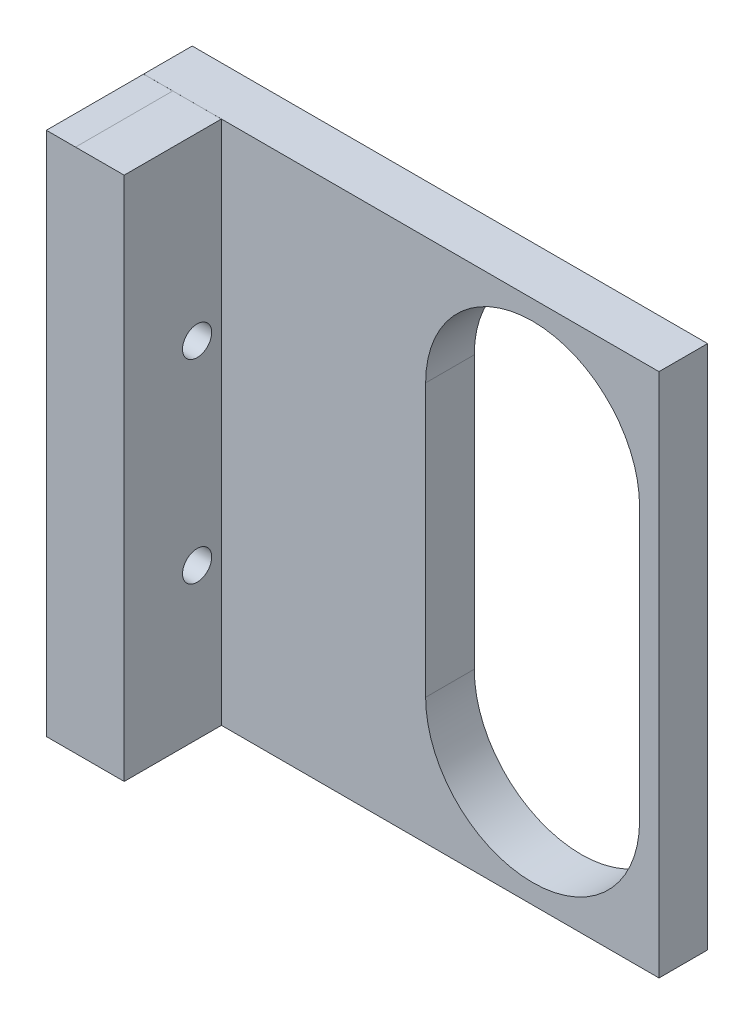
SolidWorks part; units mm, degrees
ref_plane "前视基准面" through (0, 0, 0) normal (0, 0, 1) x (1, 0, 0)
ref_plane "上视基准面" through (0, 0, 0) normal (0, 1, 0) x (1, 0, 0)
ref_plane "右视基准面" through (0, 0, 0) normal (1, 0, 0) x (0, 0, -1)
other "Configuration Table"
sketch "草图2" plane through (0, 0, 0) normal (0, 0, 1) x (1, 0, 0)
  line L0 (13, 4.25) -> (-40, 4.25)
  line L1 (-40, 4.25) -> (-40.0039, 58.25)
  line L2 (13, 4.25) -> (12.9961, 58.25)
  line L3 (-40.0039, 58.25) -> (12.9961, 58.25)
  dimension "D1" = 53
  dimension "D2" = 54
  dimension "D3" = 53
  dimension "D4" = 54
extrude "凸台-拉伸1" add sketch "草图2" along normal blind 5 contours L1 L3 L2 L0
sketch "草图3" plane through (0, 0, 0) normal (0, 0, 1) x (1, 0, 0)
  line L0 (-11, 17.25) -> (-11, 45.25)
  line L3 (11, 17.25) -> (11, 45.25)
  arc A2 (-11, 17.25) -> (11, 17.25) centre (0, 17.25) ccw
  arc A3 (-11, 45.25) -> (11, 45.25) centre (0, 45.25) cw
  point P5 (0, 17.25)
  point P7 (0, 17.25)
extrude "切除-拉伸11" cut sketch "草图3" along normal blind 5
sketch3d "3D草图1"
  point P0 (12.9892, 152.8253, 4.89)
sketch3d "3D草图2"
  point P0 (-25.1784, 27.3023, 5)
ref_plane "基准面1" through (0, 0, 5) normal (0, 0, 1) x (1, 0, 0)
sketch "草图4" plane through (0, 0, 5) normal (0, 0, 1) x (1, 0, 0)
  line L0 (-40, 4.25) -> (-37, 4.25)
  line L1 (-40.0039, 58.2474) -> (-37.0039, 58.2474)
  line L2 (-37.0039, 58.2474) -> (-37, 4.25)
  line L3 (-40.0039, 58.2474) -> (-40, 4.25)
extrude "凸台-拉伸2" add sketch "草图4" along normal blind 10
sketch3d "3D草图3"
  point P0 (-40.0017, 27.8905, 4.7154)
sketch "草图5" plane through (-39.9997, -0.0029, 0) normal (-1, -0.0001, 0) x (0, 0, 1)
  circle A0 centre (7.5, 19.7529) radius 1.5
  circle A1 centre (7.5, 39.7529) radius 1.5
extrude "切除-拉伸12" cut sketch "草图5" against normal blind 10 and the other way through all
sketch "草图6" plane through (-36.9997, -0.0027, 0) normal (1, 0.0001, 0) x (0, 0, -1)
  line L0 (-15, 58.2501) -> (-5, 58.2501)
  line L1 (-5, 58.2501) -> (-5, 4.2491)
  line L2 (-5, 4.2491) -> (-15, 4.2527)
  line L3 (-15, 4.2527) -> (-15, 58.2501)
extrude "凸台-拉伸3" add sketch "草图6" along normal blind 5
sketch "草图7" plane through (-31.9997, -0.0023, 0) normal (1, 0.0001, 0) x (0, 0, -1)
  circle A0 centre (-7.5, 39.7501) radius 1.5
  circle A1 centre (-7.5, 19.7501) radius 1.5
extrude "切除-拉伸13" cut sketch "草图7" against normal blind 5
